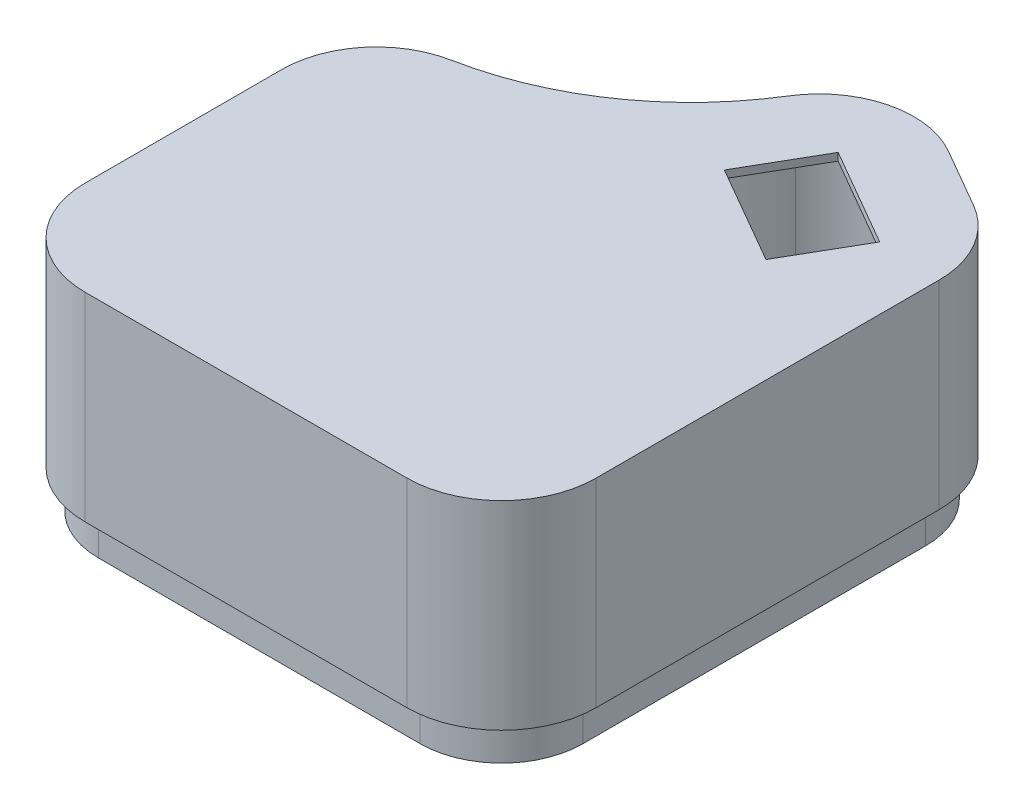
SolidWorks part; units mm, degrees
ref_plane "Front Plane" through (0, 0, 0) normal (0, 0, 1) x (1, 0, 0)
ref_plane "Top Plane" through (0, 0, 0) normal (0, 1, 0) x (1, 0, 0)
ref_plane "Right Plane" through (0, 0, 0) normal (1, 0, 0) x (0, 0, -1)
sketch "Sketch1" plane through (0, 0, 0) normal (0, 1, 0) x (1, 0, 0)
  line L1 (-130, 50) -> (130, 50)
  line L2 (-130, 50) -> (-130, -50)
  line L3 (-130, -50) -> (130, -50)
  line L4 (130, 50) -> (130, -50)
  line L5 (-130, 50) -> (130, -50) construction
  line L6 (-130, -50) -> (130, 50) construction
  point P0 (0, 0)
  dimension "D1" = 260
  dimension "D2" = 100
extrude "Boss-Extrude1" add sketch "Sketch1" along normal blind 3 contours L4 L3 L2 L1
sketch "Sketch4" plane through (0, 3, 0) normal (0, 1, 0) x (1, 0, 0)
  line L0 (-130, 50) -> (130, 50) construction
  line L1 (-77.5342, 30.2911) -> (-130, 0)
  line L2 (-130, 50) -> (-130, -50) construction
  line L3 (77.5342, 30.2911) -> (130, 0)
  line L4 (130, 50) -> (130, -50) construction
  line L5 (0, 0) -> (0, 50) construction
  line L6 (-130, -50) -> (130, -50) construction
  line L7 (-130, 0) -> (-130, 50)
  line L8 (-130, 50) -> (130, 50)
  line L9 (130, 50) -> (130, 0)
  arc A0 (-77.5342, 30.2911) -> (77.5342, 30.2911) centre (0, 50) ccw
  dimension "D1" = 160
  dimension "D2" = 60
  dimension "D3" = 60
  dimension "D4" = 50
extrude "Cut-Extrude1" cut sketch "Sketch4" against normal blind 5
sketch "Sketch5" plane through (0, 3, 0) normal (0, 1, 0) x (1, 0, 0)
  line L0 (-130, -50) -> (130, -50)
  line L1 (130, -50) -> (130, -130)
  line L2 (130, -130) -> (-130, -130)
  line L3 (-130, -130) -> (-130, -50)
  dimension "D1" = 80
extrude "Boss-Extrude4" add sketch "Sketch5" against normal blind 3
sketch "Sketch6" plane through (0, 3, 0) normal (0, 1, 0) x (1, 0, 0)
  line L6 (-79.3816, 25.7604) -> (-127, -1.7321)
  line L7 (-127, -1.7321) -> (-127, -127)
  line L8 (-127, -127) -> (127, -127)
  line L15 (127, -127) -> (127, -1.7321)
  line L16 (127, -1.7321) -> (79.3816, 25.7604)
  line L17 (-77.5342, 30.2911) -> (-130, 0)
  line L18 (-130, 0) -> (-130, -130)
  line L19 (-130, -130) -> (130, -130)
  line L20 (130, -130) -> (130, 0)
  line L27 (130, 0) -> (77.5342, 30.2911)
  line L28 (-77.5342, 30.2911) -> (-130, 0)
  line L29 (-130, 0) -> (-130, -130)
  line L30 (-130, -130) -> (130, -130)
  line L31 (130, -130) -> (130, 0)
  line L32 (130, 0) -> (77.5342, 30.2911)
  arc A3 (-79.3816, 25.7604) -> (79.3816, 25.7604) centre (0, 50) ccw
  arc A4 (-77.5342, 30.2911) -> (77.5342, 30.2911) centre (0, 50) ccw
  arc A5 (-77.5342, 30.2911) -> (77.5342, 30.2911) centre (0, 50) ccw
  dimension "D1" = 0
  dimension "D2" = 3
extrude "Boss-Extrude5" add sketch "Sketch6" along normal blind 70
sketch "Sketch7" plane through (0, 73, 0) normal (0, 1, 0) x (1, 0, 0)
  line L0 (-3.5, -32.9262) -> (-3.5, -130) construction
  line L2 (-5, -32.8493) -> (-5, -130)
  line L3 (-2, -32.9759) -> (-2, -130)
  line L4 (-2, -130) -> (-5, -130)
  line L5 (-5, 0) -> (-5, -130) construction
  line L6 (-3.5, 0) -> (-3.5, -130) construction
  line L7 (-2, 0) -> (-2, -130) construction
  line L8 (-130, -130) -> (130, -130) construction
  line L10 (-130, 0) -> (-130, -130) construction
  arc A2 (-79.3816, 25.7604) -> (79.3816, 25.7604) centre (0, 50) ccw construction
  arc A3 (-79.3816, 25.7604) -> (79.3816, 25.7604) centre (0, 50) ccw construction
  arc A4 (-5, -32.8493) -> (-2, -32.9759) centre (0, 50) ccw
  dimension "D3" = 125
  dimension "D1" = 1.5
  dimension "D2" = 1.5
extrude "Boss-Extrude6" add sketch "Sketch7" against normal up to surface (70 mm away)
sketch "Sketch9" plane through (0, 73, 0) normal (0, 1, 0) x (1, 0, 0)
  line L0 (-5, -32.8493) -> (-5, -144.8767)
  line L1 (-5, -144.8767) -> (-379.7281, -144.8767)
  line L2 (-379.7281, -144.8767) -> (-379.7281, 52.069)
  line L3 (-379.7281, 52.069) -> (-5, 52.069)
  line L4 (-5, 52.069) -> (-5, -32.8493)
extrude "Cut-Extrude3" cut sketch "Sketch9" against normal through all
sketch "Sketch10" plane through (0, 3, 0) normal (0, 1, 0) x (1, 0, 0)
  line L0 (130, -130) -> (130, 0) construction
  line L1 (14, -46.75) -> (86, -46.75) construction
  line L2 (14, -46.75) -> (14, -113.25) construction
  line L3 (14, -113.25) -> (86, -113.25) construction
  line L4 (86, -46.75) -> (86, -113.25) construction
  line L5 (14, -46.75) -> (86, -113.25) construction
  line L6 (14, -113.25) -> (86, -46.75) construction
  line L8 (-5, -130) -> (130, -130) construction
  circle A0 centre (14, -46.75) radius 5
  circle A1 centre (86, -46.75) radius 5
  circle A2 centre (86, -113.25) radius 5
  circle A3 centre (14, -113.25) radius 5
  circle A4 centre (14, -113.25) radius 1.75
  circle A5 centre (86, -113.25) radius 1.75
  circle A6 centre (14, -46.75) radius 1.75
  circle A7 centre (86, -46.75) radius 1.75
  point P0 (50, -80)
  dimension "D5" = 3.5
  dimension "D6" = 10
  dimension "D1" = 80
  dimension "D2" = 50
  dimension "D3" = 66.5
  dimension "D4" = 72
extrude "Boss-Extrude7" add sketch "Sketch10" along normal blind 50
chamfer "Chamfer1" distance 5 angle 60 4 edges at (86, 3, 108.25) (14, 3, 108.25) (86, 3, 41.75) (14, 3, 41.75)
fillet "Fillet1" radius 22 5 edges at (127, 38, 1.7321) (127, 38, 127) (-2, 38, 127) (-2, 38, 32.9759) (79.3816, 38, -25.7604)
fillet "Fillet2" radius 25 5 edges at (130, 36.5, 0) (77.5342, 36.5, -30.2911) (-5, 36.5, 29.8436) (-5, 36.5, 130) (130, 36.5, 130)
sketch "Sketch11" plane through (0, 3, 0) normal (0, 1, 0) x (1, 0, 0)
  line L1 (52.4643, -10.3946) -> (54.4317, -12.6594)
  line L4 (130, -105) -> (130, -14.4338)
  line L5 (117.5, 7.2169) -> (101.7371, 16.3176)
  line L6 (-5, -53.0776) -> (-5, -105)
  line L7 (20, -130) -> (105, -130)
  line L14 (15.2381, -28.5353) -> (15.8095, -31.4804)
  line L16 (101.7371, 16.3176) -> (100.2371, 13.7195)
  line L17 (100.2371, 13.7195) -> (116, 4.6188)
  line L18 (116, 4.6188) -> (117.5, 7.2169)
  line L19 (117.5, 7.2169) -> (101.7371, 16.3176)
  arc A0 (15.8095, -31.4804) -> (70.5398, 6.2606) centre (0, 50) ccw construction
  arc A1 (15.8095, -31.4804) -> (54.4317, -12.6594) centre (0, 50) ccw
  arc A8 (15.2381, -28.5353) -> (67.9902, 7.8415) centre (0, 50) ccw
  arc A9 (130, -14.4338) -> (117.5, 7.2169) centre (105, -14.4338) ccw
  arc A10 (101.7371, 16.3176) -> (67.9902, 7.8415) centre (89.2371, -5.333) ccw
  arc A11 (15.2381, -28.5353) -> (-5, -53.0776) centre (20, -53.0776) ccw
  arc A14 (15.2381, -28.5353) -> (52.4643, -10.3946) centre (0, 50) ccw
  arc A18 (-5, -105) -> (20, -130) centre (20, -105) ccw
  arc A19 (105, -130) -> (130, -105) centre (105, -105) ccw
  dimension "D2" = 30
  dimension "D1" = 0
extrude "Cut-Extrude4" cut sketch "Sketch11" along normal blind 20
sketch "Sketch12" plane through (0, 3, 0) normal (0, 1, 0) x (1, 0, 0)
  line L0 (105, -105) -> (15, -105) construction
  line L1 (15, -105) -> (15, -55) construction
  circle A0 centre (89.2371, -5.333) radius 1.75
  circle A1 centre (105, -105) radius 1.75
  circle A2 centre (15, -105) radius 1.75
  circle A3 centre (15, -55) radius 1.75
  dimension "D1" = 3.5
  dimension "D3" = 50
  dimension "D2" = 90
extrude "Cut-Extrude5" cut sketch "Sketch12" against normal blind 20
sketch "Sketch14" plane through (0, 23, 0) normal (0, -1, 0) x (1, 0, 0)
  line L4 (101.7371, -16.3176) -> (117.5, -7.2169)
  line L5 (117.5, -7.2169) -> (116, -4.6188)
  line L6 (116, -4.6188) -> (100.2371, -13.7195)
  line L7 (100.2371, -13.7195) -> (101.7371, -16.3176)
  line L8 (101.7371, -16.3176) -> (117.5, -7.2169)
  line L9 (117.5, -7.2169) -> (116, -4.6188)
  line L10 (116, -4.6188) -> (100.2371, -13.7195)
  line L11 (100.2371, -13.7195) -> (101.7371, -16.3176)
  dimension "D1" = 0
extrude "Cut-Extrude6" cut sketch "Sketch14" against normal blind 40
fillet "Fillet3" radius 5 8 edges at (53.448, 3, 11.527) (53.448, 23, 11.527) (15.5238, 23, 30.0079) (15.5238, 3, 30.0079) (100.9871, 63, -15.0186) (116.75, 63, -5.9178) (116.75, 3, -5.9178) (100.9871, 3, -15.0186)
sketch "Sketch15" plane through (0, 73, 0) normal (0, 1, 0) x (1, 0, 0)
  line L0 (126.5, -105) -> (126.5, -14.4338)
  line L1 (115.75, 4.1858) -> (99.9871, 13.2865)
  line L2 (-1.5, -53.0776) -> (-1.5, -105)
  line L3 (20, -126.5) -> (105, -126.5)
  line L4 (130, -105) -> (130, -14.4338)
  line L5 (117.5, 7.2169) -> (101.7371, 16.3176)
  line L6 (-5, -53.0776) -> (-5, -105)
  line L7 (20, -130) -> (105, -130)
  line L8 (130, -105) -> (130, -14.4338) construction
  line L9 (117.5, 7.2169) -> (101.7371, 16.3176) construction
  line L10 (-5, -53.0776) -> (-5, -105) construction
  line L11 (20, -130) -> (105, -130) construction
  line L12 (124.5, -105) -> (124.5, -14.4338)
  line L13 (114.75, 2.4537) -> (98.9871, 11.5545)
  line L14 (0.5, -53.0776) -> (0.5, -105)
  line L15 (20, -124.5) -> (105, -124.5)
  arc A0 (126.5, -14.4338) -> (115.75, 4.1858) centre (105, -14.4338) ccw
  arc A1 (99.9871, 13.2865) -> (70.9647, 5.9971) centre (89.2371, -5.333) ccw
  arc A2 (15.9048, -31.9713) -> (70.9647, 5.9971) centre (0, 50) ccw
  arc A3 (15.9048, -31.9713) -> (-1.5, -53.0776) centre (20, -53.0776) ccw
  arc A4 (-1.5, -105) -> (20, -126.5) centre (20, -105) ccw
  arc A5 (105, -126.5) -> (126.5, -105) centre (105, -105) ccw
  arc A6 (130, -14.4338) -> (117.5, 7.2169) centre (105, -14.4338) ccw
  arc A7 (101.7371, 16.3176) -> (67.9902, 7.8415) centre (89.2371, -5.333) ccw
  arc A8 (15.2381, -28.5353) -> (67.9902, 7.8415) centre (0, 50) ccw
  arc A9 (15.2381, -28.5353) -> (-5, -53.0776) centre (20, -53.0776) ccw
  arc A10 (-5, -105) -> (20, -130) centre (20, -105) ccw
  arc A11 (105, -130) -> (130, -105) centre (105, -105) ccw
  arc A12 (130, -14.4338) -> (117.5, 7.2169) centre (105, -14.4338) ccw construction
  arc A13 (101.7371, 16.3176) -> (67.9902, 7.8415) centre (89.2371, -5.333) ccw construction
  arc A14 (15.2381, -28.5353) -> (67.9902, 7.8415) centre (0, 50) ccw construction
  arc A15 (15.2381, -28.5353) -> (-5, -53.0776) centre (20, -53.0776) ccw construction
  arc A16 (-5, -105) -> (20, -130) centre (20, -105) ccw construction
  arc A17 (105, -130) -> (130, -105) centre (105, -105) ccw construction
  arc A18 (124.5, -14.4338) -> (114.75, 2.4537) centre (105, -14.4338) ccw
  arc A19 (98.9871, 11.5545) -> (72.6645, 4.9431) centre (89.2371, -5.333) ccw
  arc A20 (16.2857, -33.9347) -> (72.6645, 4.9431) centre (0, 50) ccw
  arc A21 (16.2857, -33.9347) -> (0.5, -53.0776) centre (20, -53.0776) ccw
  arc A22 (0.5, -105) -> (20, -124.5) centre (20, -105) ccw
  arc A23 (105, -124.5) -> (124.5, -105) centre (105, -105) ccw
  dimension "D1" = 0
  dimension "D2" = 3.5
  dimension "D3" = 2
extrude "Boss-Extrude8" add sketch "Sketch15" along normal blind 10 separate body
sketch "Sketch16" plane through (0, 0, 0) normal (0, 0, 1) x (1, 0, 0)
  line L0 (-5, 73) -> (130, 73)
  line L1 (130, 73) -> (130, 0)
  line L2 (130, 0) -> (-5, 0)
  line L3 (-5, 0) -> (-5, 73)
extrude "Cut-Extrude7" cut sketch "Sketch16" against normal through all both and the other way through all
sketch "Sketch17" plane through (0, 83, 0) normal (0, 1, 0) x (1, 0, 0)
  line L0 (130, -105) -> (130, -14.4338)
  line L1 (117.5, 7.2169) -> (101.7371, 16.3176)
  line L2 (-5, -53.0776) -> (-5, -105)
  line L3 (20, -130) -> (105, -130)
  line L4 (126.5, -105) -> (126.5, -14.4338)
  line L5 (115.75, 4.1858) -> (99.9871, 13.2865)
  line L6 (-1.5, -53.0776) -> (-1.5, -105)
  line L7 (20, -126.5) -> (105, -126.5)
  line L8 (126.5, -105) -> (126.5, -14.4338) construction
  line L9 (115.75, 4.1858) -> (99.9871, 13.2865) construction
  line L10 (-1.5, -53.0776) -> (-1.5, -105) construction
  line L11 (20, -126.5) -> (105, -126.5) construction
  arc A0 (130, -14.4338) -> (117.5, 7.2169) centre (105, -14.4338) ccw
  arc A1 (101.7371, 16.3176) -> (67.9902, 7.8415) centre (89.2371, -5.333) ccw
  arc A2 (15.2381, -28.5353) -> (67.9902, 7.8415) centre (0, 50) ccw
  arc A3 (15.2381, -28.5353) -> (-5, -53.0776) centre (20, -53.0776) ccw
  arc A4 (-5, -105) -> (20, -130) centre (20, -105) ccw
  arc A5 (105, -130) -> (130, -105) centre (105, -105) ccw
  arc A6 (105, -126.5) -> (126.5, -105) centre (105, -105) ccw
  arc A7 (126.5, -14.4338) -> (115.75, 4.1858) centre (105, -14.4338) ccw
  arc A8 (99.9871, 13.2865) -> (70.9647, 5.9971) centre (89.2371, -5.333) ccw
  arc A9 (15.9048, -31.9713) -> (70.9647, 5.9971) centre (0, 50) ccw
  arc A10 (15.9048, -31.9713) -> (-1.5, -53.0776) centre (20, -53.0776) ccw
  arc A11 (-1.5, -105) -> (20, -126.5) centre (20, -105) ccw
  arc A12 (105, -126.5) -> (126.5, -105) centre (105, -105) ccw construction
  arc A13 (126.5, -14.4338) -> (115.75, 4.1858) centre (105, -14.4338) ccw construction
  arc A14 (99.9871, 13.2865) -> (70.9647, 5.9971) centre (89.2371, -5.333) ccw construction
  arc A15 (15.9048, -31.9713) -> (70.9647, 5.9971) centre (0, 50) ccw construction
  arc A16 (15.9048, -31.9713) -> (-1.5, -53.0776) centre (20, -53.0776) ccw construction
  arc A17 (-1.5, -105) -> (20, -126.5) centre (20, -105) ccw construction
  dimension "D1" = 0
  dimension "D2" = 3.5
extrude "Boss-Extrude9" add sketch "Sketch17" along normal blind 52.54
sketch "Sketch18" plane through (0, 135.54, 0) normal (0, 1, 0) x (1, 0, 0)
  line L0 (87.4519, 1.4711) -> (113.4327, -13.5289)
  line L1 (113.4327, -13.5289) -> (102.4327, -32.5814)
  line L2 (102.4327, -32.5814) -> (76.4519, -17.5814)
  line L3 (76.4519, -17.5814) -> (87.4519, 1.4711)
  line L4 (117.5, 7.2169) -> (101.7371, 16.3176) construction
  arc A0 (15.2381, -28.5353) -> (67.9902, 7.8415) centre (0, 50) ccw construction
  dimension "D1" = 30
  dimension "D2" = 22
  dimension "D3" = 20
  dimension "D4" = 100
extrude "Cut-Extrude8" cut sketch "Sketch18" against normal blind 5
sketch "Sketch20" plane through (0, 83, 0) normal (0, -1, 0) x (1, 0, 0)
  line L4 (124.5, 14.4338) -> (124.5, 105)
  line L5 (105, 124.5) -> (20, 124.5)
  line L6 (0.5, 105) -> (0.5, 53.0776)
  line L7 (98.9871, -11.5545) -> (114.75, -2.4537)
  line L8 (124.5, 14.4338) -> (124.5, 105)
  line L9 (105, 124.5) -> (20, 124.5)
  line L10 (0.5, 105) -> (0.5, 53.0776)
  line L11 (98.9871, -11.5545) -> (114.75, -2.4537)
  arc A6 (124.5, 105) -> (105, 124.5) centre (105, 105) ccw
  arc A7 (20, 124.5) -> (0.5, 105) centre (20, 105) ccw
  arc A8 (0.5, 53.0776) -> (16.2857, 33.9347) centre (20, 53.0776) ccw
  arc A9 (72.6645, -4.9431) -> (16.2857, 33.9347) centre (0, -50) ccw
  arc A10 (72.6645, -4.9431) -> (98.9871, -11.5545) centre (89.2371, 5.333) ccw
  arc A11 (114.75, -2.4537) -> (124.5, 14.4338) centre (105, 14.4338) ccw
  arc A12 (124.5, 105) -> (105, 124.5) centre (105, 105) ccw
  arc A13 (20, 124.5) -> (0.5, 105) centre (20, 105) ccw
  arc A14 (0.5, 53.0776) -> (16.2857, 33.9347) centre (20, 53.0776) ccw
  arc A15 (72.6645, -4.9431) -> (16.2857, 33.9347) centre (0, -50) ccw
  arc A16 (72.6645, -4.9431) -> (98.9871, -11.5545) centre (89.2371, 5.333) ccw
  arc A17 (114.75, -2.4537) -> (124.5, 14.4338) centre (105, 14.4338) ccw
  dimension "D1" = 0
extrude "Cut-Extrude10" cut sketch "Sketch20" against normal offset from surface (50.54 mm away) 2 up to face at (94.9423, 135.54, 15.5551)
